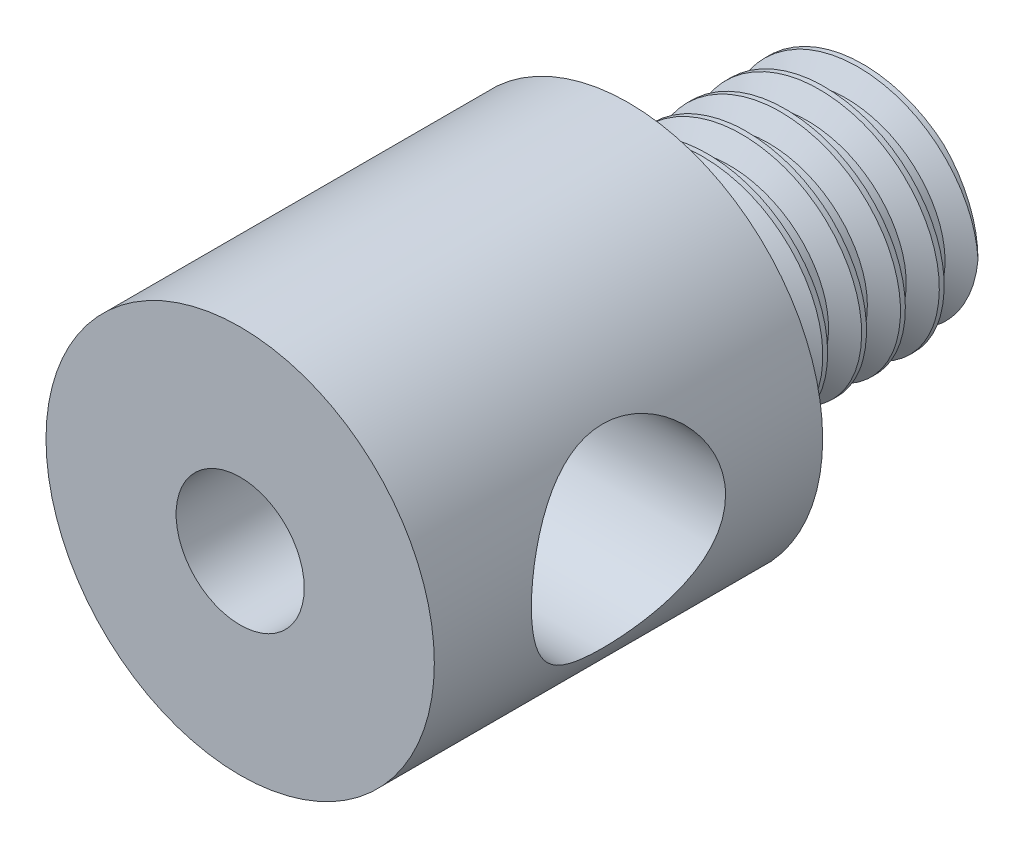
SolidWorks part; units mm, degrees
ref_plane "Front Plane" through (0, 0, 0) normal (0, 0, 1) x (1, 0, 0)
ref_plane "Top Plane" through (0, 0, 0) normal (0, 1, 0) x (1, 0, 0)
ref_plane "Right Plane" through (0, 0, 0) normal (1, 0, 0) x (0, 0, -1)
sketch "Sketch3" plane through (0, 0, 0) normal (0, 0, 1) x (1, 0, 0)
  circle A0 centre (-2.9808, 0.6857) radius 5
  dimension "D1" = 10
extrude "Boss-Extrude2" add sketch "Sketch3" along normal blind 10
ref_plane "Plane1" through (-7.9808, 0, 0) normal (-1, 0, 0) x (0, 0, 1)
sketch "Sketch4" plane through (-7.9808, 0, 0) normal (-1, 0, 0) x (0, 0, 1)
  line L0 (10, -4.3143) -> (10, 5.6857) construction
  line L1 (10, 5.6857) -> (0, 5.6857) construction
  circle A0 centre (5, 0.6857) radius 2.5
  dimension "D1" = 5
  dimension "D2" = 5
  dimension "D3" = 5
extrude "Cut-Extrude1" cut sketch "Sketch4" against normal through all
sketch "Sketch5" plane through (0, 0, 10) normal (0, 0, 1) x (1, 0, 0)
  circle A0 centre (-2.9808, 0.6857) radius 5 construction
  point P0 (-2.9808, 0.6857)
  point P1 (0, 0)
hole_wizard "M4x0.7 Tapped Hole1" positions "Sketch6" profile "Sketch7" tap size "M4x0.7" standard "BSI"
sketch "Sketch6" plane through (0, 0, 10) normal (0, 0, 1) x (1, 0, 0)
  point P0 (-2.9808, 0.6857)
sketch "Sketch7" plane through (-2.9808, 0.6857, 10) normal (1, 0, 0) x (0, -1, 0)
  line L0 (0, 0) -> (0, 5.9914)
  line L1 (0, 5.9914) -> (1.65, 5)
  line L2 (1.65, 5) -> (1.65, 0)
  line L5 (1.65, 0) -> (0, 0)
  line L10 (0, 5.9914) -> (-1.65, 5) construction
  line L11 (0, -6.35) -> (0, 107.95) construction
  dimension "Tap Drill Dia." = 3.3
  dimension "Tap Drill Depth" = 5
  dimension "Drill Angle" = 118
cosmetic thread "Hole Thread1" parameters "D1"=8, "D2"=4
sketch "Sketch8" plane through (0, 0, 0) normal (0, 0, -1) x (-1, 0, 0)
  circle A0 centre (2.9808, 0.6857) radius 3
  circle A1 centre (2.9808, 0.6857) radius 5 construction
  dimension "D1" = 6
extrude "Boss-Extrude3" add sketch "Sketch8" along normal blind 6
thread "Thread2" pitch 1 method cut profile "Thread Profile2" start angle 0, offset 1, length 0, pitch 1, diameter 6
ref_plane "Plane3" through (0.0192, 0.6857, -7) normal (0, -1, 0) x (1, 0, 0)
sketch "Thread Profile2" plane through (0.0192, 0.6857, -7) normal (0, -1, 0) x (1, 0, 0)
  line L0 (0, 0) -> (0, 1) construction
  line L11 (0, 0) -> (0, 0.875)
  line L12 (0, 0.875) -> (-0.5413, 0.5625)
  line L13 (-0.5413, 0.5625) -> (-0.5413, 0.3125)
  line L15 (-0.5413, 0.3125) -> (0, 0)
  line L17 (-0.5413, 0.4375) -> (0, 0.4375) construction
  point P2 (0, 0)
  dimension "Pitch" = 1
  dimension "Profile_Angle" = 60
  dimension "Profile_Land" = 0.25
  dimension "Profile_Height" = 0.5413
